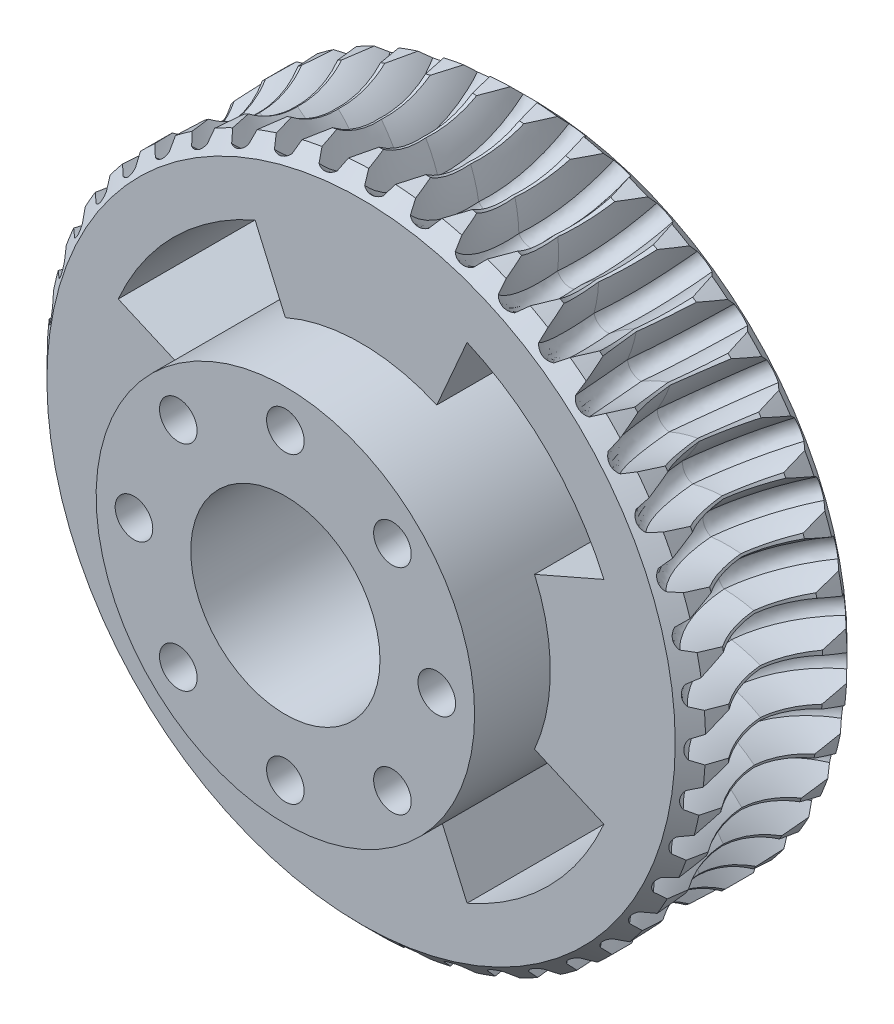
SolidWorks part; units mm, degrees
ref_plane "Front Plane" through (0, 0, 0) normal (0, 0, 1) x (1, 0, 0)
ref_plane "Top Plane" through (0, 0, 0) normal (0, 1, 0) x (1, 0, 0)
ref_plane "Right Plane" through (0, 0, 0) normal (1, 0, 0) x (0, 0, -1)
sketch "Sketch1" plane through (0, 0, 0) normal (0, 0, 1) x (1, 0, 0)
  circle A0 centre (0, 0) radius 43.5
  circle A1 centre (0, 0) radius 12.5
  dimension "D1" = 87
  dimension "D2" = 25
extrude "Boss-Extrude1" add sketch "Sketch1" along normal mid plane 22.7
chamfer "Chamfer1" distance 2 angle 45 2 edges at (43.5, 0, -11.35) (43.5, 0, 11.35)
sketch "Sketch2" plane through (0, 0, 0) normal (1, 0, 0) x (0, 0, -1)
  line L0 (0, 0) -> (-11.35, 0) construction
  line L1 (-11.35, 41.5) -> (-11.35, -41.5) construction
  line L2 (0, 0) -> (0, -52) construction
  circle A0 centre (0, -52) radius 10.5
  dimension "D1" = 21
  dimension "D2" = 52
revolve "Cut-Revolve1" cut sketch "Sketch2" angle 360 about L0
sketch "Sketch3" plane through (0, 0, 0) normal (1, 0, 0) x (0, 0, -1)
  circle A1 centre (0, -52) radius 10.5
  circle A2 centre (0, -52) radius 10.5
  dimension "D1" = 0
curve "Helix/Spiral2" pitch 6 height 1.5 turns 0.25
sketch "Sketch4" plane through (0, 0, 0) normal (0, 0, 1) x (1, 0, 0)
  line L0 (0, 0) -> (0, -43.5) construction
  line L1 (-3.45, -42.44) -> (-3.45, -46.04)
  line L2 (-3.45, -46.04) -> (3.45, -46.04)
  line L3 (3.45, -46.04) -> (3.45, -42.44)
  circle A0 centre (0, 0) radius 43.5 construction
  arc A1 (-1.2018, -37.79) -> (1.2018, -37.79) centre (0, -39.13) cw
  arc A2 (-1.2018, -37.79) -> (-3.45, -42.44) centre (-18.3636, -32.3611) cw
  arc A3 (1.2018, -37.79) -> (3.45, -42.44) centre (18.3636, -32.3611) ccw
  dimension "D2" = 1.8
  dimension "D3" = 18
  dimension "D7" = 1.34
  dimension "D1" = 39.13
  dimension "D4" = 4.65
  dimension "D5" = 6.9
  dimension "D6" = 3.6
sweep "Cut-Sweep1" cut profiles "Sketch4" path "Helix/Spiral2" align with end faces yes
sketch "Sketch5" plane through (0, 0, 0) normal (1, 0, 0) x (0, 0, -1)
  circle A1 centre (0, -52) radius 10.5
  circle A2 centre (0, -52) radius 10.5
  dimension "D1" = 0
curve "Helix/Spiral3" pitch 6 height 1.5 turns 0.25
sketch "Sketch6" plane through (0, 0, 0) normal (0, 0, 1) x (1, 0, 0)
  line L3 (-3.45, -42.44) -> (-3.45, -46.04)
  line L4 (-3.45, -46.04) -> (3.45, -46.04)
  line L5 (3.45, -46.04) -> (3.45, -42.44)
  line L6 (-3.45, -42.44) -> (-3.45, -46.04)
  line L7 (-3.45, -46.04) -> (3.45, -46.04)
  line L8 (3.45, -46.04) -> (3.45, -42.44)
  arc A3 (1.2018, -37.79) -> (3.45, -42.44) centre (18.3636, -32.3611) ccw
  arc A4 (1.2018, -37.79) -> (-1.2018, -37.79) centre (0, -39.13) ccw
  arc A5 (-3.45, -42.44) -> (-1.2018, -37.79) centre (-18.3636, -32.3611) ccw
  arc A6 (1.2018, -37.79) -> (3.45, -42.44) centre (18.3636, -32.3611) ccw
  arc A7 (1.2018, -37.79) -> (-1.2018, -37.79) centre (0, -39.13) ccw
  arc A8 (-3.45, -42.44) -> (-1.2018, -37.79) centre (-18.3636, -32.3611) ccw
  dimension "D1" = 0
sweep "Cut-Sweep2" cut profiles "Sketch6" path "Helix/Spiral3"
pattern_circular "CirPattern1" count 44 over 360 about axis through (0, 0, -11.35) along (0, 0, 1) of "Cut-Sweep2", "Cut-Sweep1"
sketch "Sketch7" plane through (0, 0, 11.35) normal (0, 0, 1) x (1, 0, 0)
  circle A0 centre (0, 0) radius 25
  circle A1 centre (0, 0) radius 12.5
  dimension "D1" = 50
  dimension "D2" = 25
extrude "Boss-Extrude2" add sketch "Sketch7" along normal blind 10
sketch "Sketch8" plane through (0, 0, 21.35) normal (0, 0, 1) x (1, 0, 0)
  circle A1 centre (0, 20) radius 2.4853
  circle A2 centre (14.1421, 14.1421) radius 2.4853
  circle A3 centre (20, 0) radius 2.4853
  circle A4 centre (14.1421, -14.1421) radius 2.4853
  circle A5 centre (0, -20) radius 2.4853
  circle A6 centre (-14.1421, -14.1421) radius 2.4853
  circle A7 centre (-20, 0) radius 2.4853
  circle A8 centre (-14.1421, 14.1421) radius 2.4853
  point P21 (0, 0)
  dimension "D2" = 8
extrude "Cut-Extrude1" cut sketch "Sketch8" against normal blind 6
sketch "Sketch11" plane through (0, 0, 11.35) normal (0, 0, 1) x (1, 0, 0)
  line L0 (0, -50.8705) -> (0, 48.3322) construction
  line L1 (-53.0914, 0) -> (62.081, 0) construction
  line L2 (-10, 22.9129) -> (-14, 32.078)
  line L3 (-22.9129, 10) -> (-32.078, 14)
  line L4 (10, 22.9129) -> (14, 32.078)
  line L5 (-22.9129, -10) -> (-32.078, -14)
  line L6 (10, -22.9129) -> (14, -32.078)
  line L7 (-10, -22.9129) -> (-14, -32.078)
  line L8 (22.9129, 10) -> (32.078, 14)
  line L9 (22.9129, -10) -> (32.078, -14)
  arc A0 (-32.078, -14) -> (-14, -32.078) centre (0, 0) ccw
  arc A1 (-22.9129, -10) -> (-10, -22.9129) centre (0, 0) ccw
  arc A2 (22.9129, 10) -> (10, 22.9129) centre (0, 0) ccw
  arc A3 (32.078, 14) -> (14, 32.078) centre (0, 0) ccw
  arc A4 (-10, 22.9129) -> (-22.9129, 10) centre (0, 0) ccw
  arc A5 (-14, 32.078) -> (-32.078, 14) centre (0, 0) ccw
  arc A6 (10, -22.9129) -> (22.9129, -10) centre (0, 0) ccw
  arc A7 (14, -32.078) -> (32.078, -14) centre (0, 0) ccw
  dimension "D1" = 70
  dimension "D2" = 50
  dimension "D3" = 10
  dimension "D4" = 10
extrude "Cut-Extrude2" cut sketch "Sketch11" against normal through all
